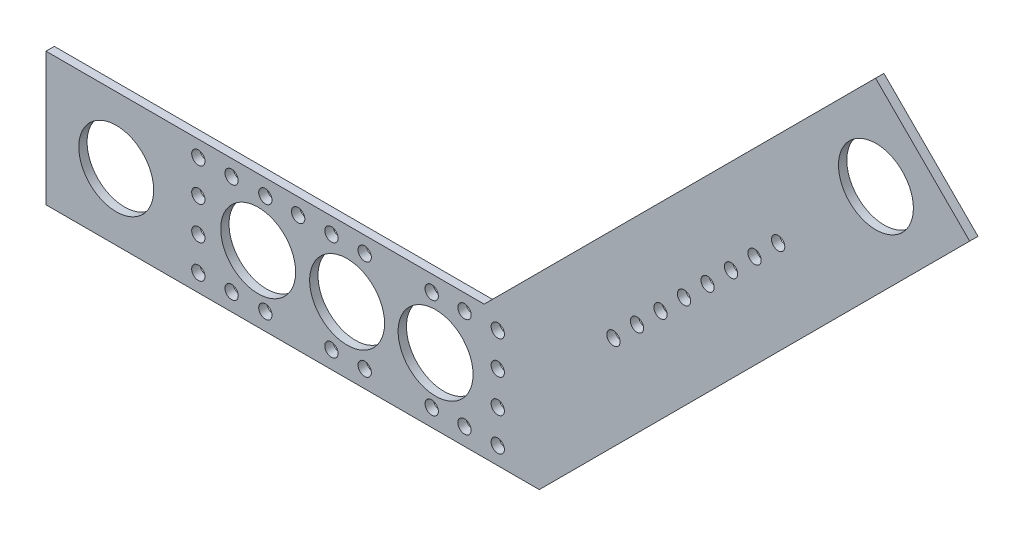
SolidWorks part; units mm, degrees
ref_plane "Front Plane" through (0, 0, 0) normal (0, 0, 1) x (1, 0, 0)
ref_plane "Top Plane" through (0, 0, 0) normal (0, 1, 0) x (1, 0, 0)
ref_plane "Right Plane" through (0, 0, 0) normal (1, 0, 0) x (0, 0, -1)
sketch "Sketch1" plane through (0, 0, 0) normal (0, 0, 1) x (1, 0, 0)
  line L0 (-59.6938, 4.2713) -> (-59.6938, -46.5287)
  line L1 (-59.6938, -46.5287) -> (128.6141, -46.5287)
  line L2 (128.6141, -46.5287) -> (292.9114, 117.7686)
  line L3 (292.9114, 117.7686) -> (256.9904, 153.6896)
  line L4 (256.9904, 153.6896) -> (107.5721, 4.2713)
  line L5 (107.5721, 4.2713) -> (-59.6938, 4.2713)
  circle A10 centre (11.1589, -1.8121) radius 2.54 construction
  circle A11 centre (24.0402, -1.8121) radius 2.54 construction
  circle A12 centre (36.5589, -1.8121) radius 2.54 construction
  circle A13 centre (49.2589, -1.8121) radius 2.54 construction
  circle A14 centre (61.9589, -1.8121) radius 2.54 construction
  circle A15 centre (87.5402, -1.8121) radius 2.54 construction
  circle A16 centre (100.0589, -1.8121) radius 2.54 construction
  circle A17 centre (112.7589, -1.8121) radius 2.54 construction
  circle A18 centre (112.7589, -14.5121) radius 2.54 construction
  circle A19 centre (112.7589, -27.2121) radius 2.54 construction
  circle A20 centre (112.7589, -39.9121) radius 2.54 construction
  circle A21 centre (100.0589, -39.9121) radius 2.54 construction
  circle A22 centre (87.5402, -39.9121) radius 2.54 construction
  circle A23 centre (61.9589, -39.9121) radius 2.54 construction
  circle A24 centre (49.2589, -39.9121) radius 2.54 construction
  circle A25 centre (24.0402, -39.9121) radius 2.54 construction
  circle A26 centre (11.1589, -39.9121) radius 2.54 construction
  circle A27 centre (-1.5411, -39.9121) radius 2.54 construction
  circle A28 centre (-1.5411, -27.2121) radius 2.54 construction
  circle A29 centre (-1.5411, -14.5121) radius 2.54 construction
  circle A30 centre (-1.5411, -1.8121) radius 2.54 construction
  circle A36 centre (55.2538, -21.1287) radius 14.3002 construction
  circle A37 centre (-32.8842, -21.1287) radius 14.3002 construction
  circle A48 centre (11.1589, -1.8121) radius 2.54
  circle A49 centre (24.0402, -1.8121) radius 2.54
  circle A50 centre (36.5589, -1.8121) radius 2.54
  circle A51 centre (49.2589, -1.8121) radius 2.54
  circle A52 centre (61.9589, -1.8121) radius 2.54
  circle A53 centre (87.5402, -1.8121) radius 2.54
  circle A54 centre (100.0589, -1.8121) radius 2.54
  circle A55 centre (112.7589, -1.8121) radius 2.54
  circle A56 centre (112.7589, -14.5121) radius 2.54
  circle A57 centre (112.7589, -27.2121) radius 2.54
  circle A58 centre (112.7589, -39.9121) radius 2.54
  circle A59 centre (100.0589, -39.9121) radius 2.54
  circle A60 centre (87.5402, -39.9121) radius 2.54
  circle A61 centre (61.9589, -39.9121) radius 2.54
  circle A62 centre (49.2589, -39.9121) radius 2.54
  circle A63 centre (24.0402, -39.9121) radius 2.54
  circle A64 centre (11.1589, -39.9121) radius 2.54
  circle A65 centre (-1.5411, -39.9121) radius 2.54
  circle A66 centre (-1.5411, -27.2121) radius 2.54
  circle A67 centre (-1.5411, -14.5121) radius 2.54
  circle A68 centre (-1.5411, -1.8121) radius 2.54
  circle A74 centre (55.2538, -21.1287) radius 14.3002
  circle A75 centre (-32.8842, -21.1287) radius 14.3002
  circle A76 centre (257.1207, 117.8989) radius 14.3002
  circle A77 centre (21.3013, -21.1287) radius 14.3002
  circle A78 centre (89.024, -21.1287) radius 14.3002
  circle A79 centre (156.927, 17.7052) radius 2.54
  circle A80 centre (165.9073, 26.6854) radius 2.54
  circle A81 centre (174.8875, 35.6657) radius 2.54
  circle A82 centre (183.8678, 44.646) radius 2.54
  circle A83 centre (192.8481, 53.6262) radius 2.54
  circle A84 centre (201.8283, 62.6065) radius 2.54
  circle A85 centre (210.8086, 71.5867) radius 2.54
  circle A86 centre (219.7888, 80.567) radius 2.54
  dimension "D4" = 245.11
  dimension "D6" = 33.7702
  dimension "D7" = 25.4
  dimension "D1" = 50.8
  dimension "D2" = 50.8
  dimension "D3" = 135
  dimension "D5" = 25.4
  dimension "D8" = 8
extrude "Boss-Extrude1" add sketch "Sketch1" along normal blind 3.175
